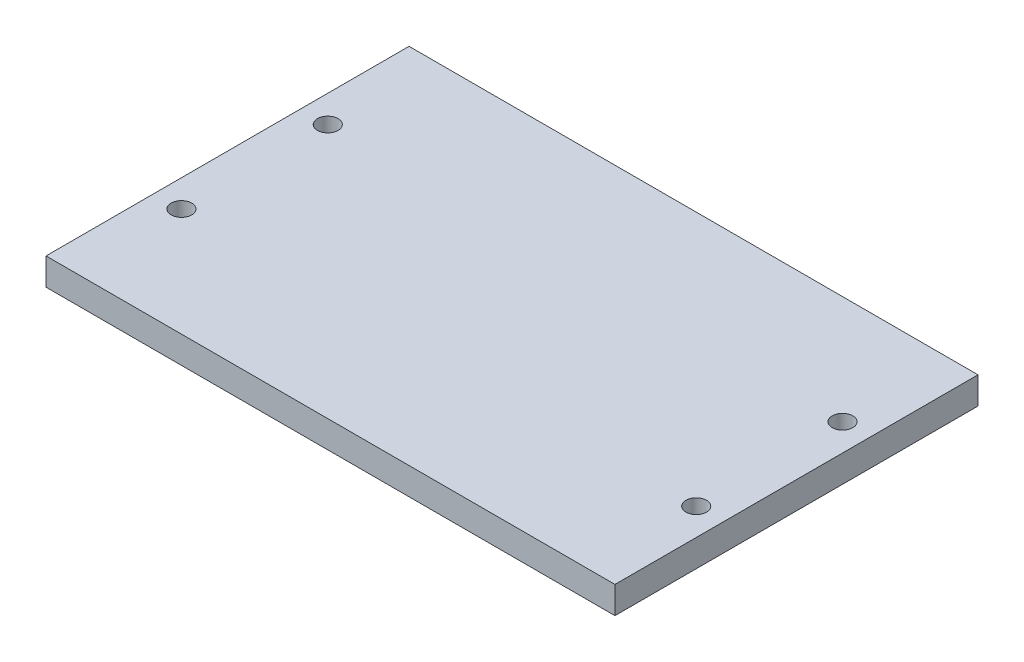
SolidWorks part; units mm, degrees
material "1060 Alloy"
ref_plane "Front Plane" through (0, 0, 0) normal (0, 0, 1) x (1, 0, 0)
ref_plane "Top Plane" through (0, 0, 0) normal (0, 1, 0) x (1, 0, 0)
ref_plane "Right Plane" through (0, 0, 0) normal (1, 0, 0) x (0, 0, -1)
sketch "Sketch1" plane through (0, 0, 0) normal (0, 1, 0) x (1, 0, 0)
  line L1 (-45.1884, 47.6545) -> (88.1616, 47.6545)
  line L2 (-45.1884, 47.6545) -> (-45.1884, -37.4355)
  line L3 (-45.1884, -37.4355) -> (88.1616, -37.4355)
  line L4 (88.1616, 47.6545) -> (88.1616, -37.4355)
  dimension "D1" = 133.35
  dimension "D2" = 85.09
extrude "Boss-Extrude1" add sketch "Sketch1" along normal blind 6.35
sketch "Sketch2" plane through (0, 6.35, 0) normal (0, 1, 0) x (1, 0, 0)
  line L0 (88.1616, -37.4355) -> (88.1616, 47.6545) construction
  line L1 (-45.1884, -37.4355) -> (88.1616, -37.4355) construction
  line L3 (88.1616, 47.6545) -> (-45.1884, 47.6545) construction
  line L4 (-45.1884, 47.6545) -> (-45.1884, -37.4355) construction
  circle A0 centre (81.8116, -12.0355) radius 2.413
  circle A1 centre (81.8116, 22.2545) radius 2.413
  circle A2 centre (-38.8384, 22.2545) radius 2.413
  circle A3 centre (-38.8384, -12.0355) radius 2.413
  point P0 (81.8116, -12.0355)
  point P1 (-38.8384, -12.0355)
  point P2 (81.8116, 22.2545)
  point P9 (-38.8384, 22.2545)
  dimension "D5" = 4.826
  dimension "D1" = 6.35
  dimension "D2" = 6.35
  dimension "D3" = 25.4
  dimension "D4" = 25.4
extrude "Cut-Extrude1" cut sketch "Sketch2" against normal through all
